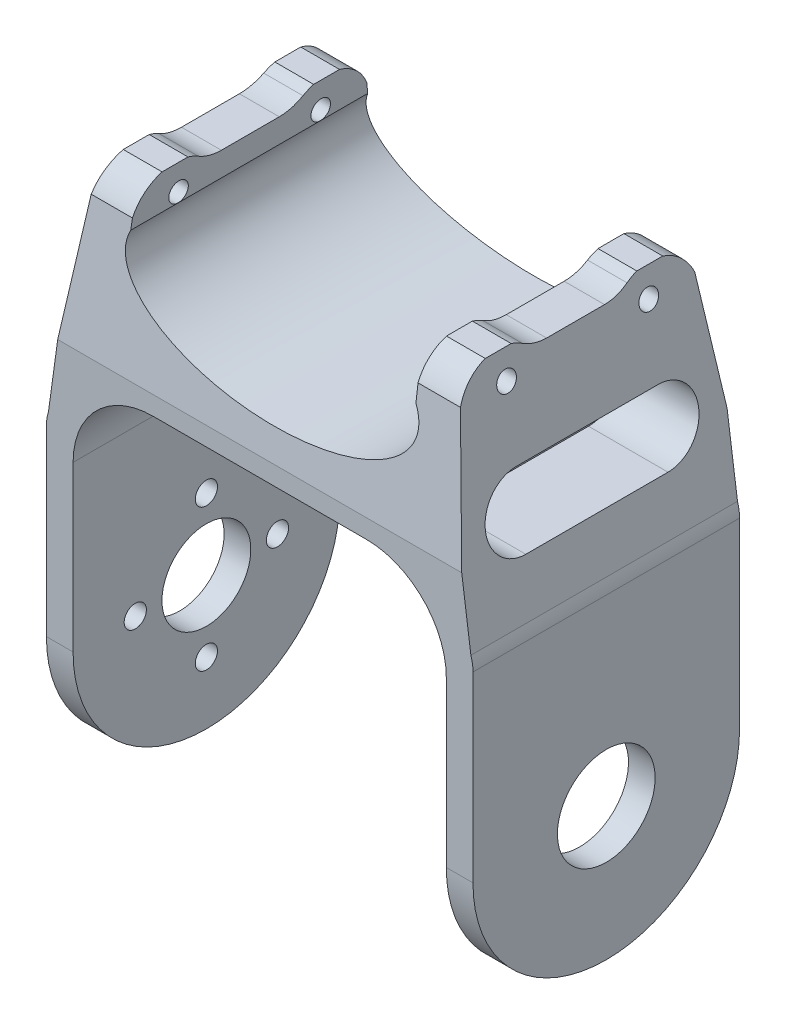
SolidWorks part; units mm, degrees
note: The reader was unsure of these and kept them because the rebuilt part matched: shared geometry of "Эскиз3<4>".
ref_plane "Спереди" through (0, 0, 0) normal (0, 0, 1) x (1, 0, 0)
ref_plane "Сверху" through (0, 0, 0) normal (0, 1, 0) x (1, 0, 0)
ref_plane "Справа" through (0, 0, 0) normal (1, 0, 0) x (0, 0, -1)
sketch "Эскиз1" plane through (0, 0, 0) normal (0, 0, 1) x (1, 0, 0)
  line L0 (-0.5529, 19.3299) -> (-0.5529, 52.5803) construction
  line L1 (-0.5529, 19.3299) -> (-0.5529, -49.2992) construction
  line L2 (23.2129, 9.6952) -> (19.8144, 34.416)
  line L3 (-21.5529, -27.3669) -> (-24.5529, -27.3669)
  line L4 (-16.7372, 30.3068) -> (-16.5529, 34.416)
  line L5 (-21.5529, -27.3669) -> (-21.5529, 5.955)
  line L6 (-24.5529, -27.3669) -> (-24.5529, 8.1828)
  line L7 (-20.9202, 34.416) -> (-16.5529, 34.416)
  line L8 (-24.3187, 9.6952) -> (-20.9202, 34.416)
  line L15 (-0.5529, 46.1948) -> (-0.6138, 46.2579)
  line L16 (-21.5529, 5.955) -> (-21.5529, 6.1114)
  line L17 (11.4471, 15.1114) -> (-12.5529, 15.1114)
  line L21 (15.4471, 29.6011) -> (15.4471, 34.416)
  line L24 (20.4471, 5.955) -> (20.4471, 6.1114)
  line L25 (-0.5529, 46.1948) -> (-0.492, 46.2579)
  line L34 (23.4471, -27.3669) -> (23.4471, 8.1828)
  line L35 (20.4471, -27.3669) -> (20.4471, 5.955)
  line L36 (19.8144, 34.416) -> (15.4471, 34.416)
  line L37 (20.4471, -27.3669) -> (23.4471, -27.3669)
  arc A0 (-12.5529, 15.1114) -> (-21.5529, 6.1114) centre (-12.5529, 6.1114) ccw
  arc A1 (11.4471, 15.1114) -> (20.4471, 6.1114) centre (11.4471, 6.1114) cw
  arc A2 (23.4471, 8.1828) -> (23.2129, 9.6952) centre (18.4471, 8.1828) ccw
  arc A19 (-24.3187, 9.6952) -> (-24.5529, 8.1828) centre (-19.5529, 8.1828) ccw
  ellipse E0 centre (-0.5529, 28.1714) end of major axis (15.9987, 27.4808) minor radius 7.6153 (-16.7372, 30.3068) -> (15.4471, 29.6011) ccw
  point P40 (-0.5529, 15.1114)
  point P54 (23.4471, 8.9571)
  point P105 (-24.5529, 8.9571)
  dimension "D2" = 9
  dimension "D3" = 5
  dimension "D5" = 21
  dimension "D10" = 61.7828
  dimension "D1" = 37.0621
  dimension "D4" = 16
  dimension "D6" = 24
  dimension "D7" = 187.828
  dimension "D8" = 9.1563
  dimension "D13" = 34.416
  dimension "D16" = 0.5529
  dimension "D17" = 27.3669
  dimension "D18" = 23.7658
  dimension "D29" = 5.4606
extrude "Бобышка-Вытянуть1" add sketch "Эскиз1" along normal blind 30
sketch "Эскиз2" plane through (23.4471, 0, 0) normal (1, 0, 0) x (0, 0, -1)
  line L0 (-15, -27.3669) -> (-15, 46.6662) construction
  line L1 (-30, -27.3669) -> (0, -27.3669) construction
  line L2 (-6.4725, 34.6331) -> (-23.5275, 34.6331)
  line L3 (-30.3535, 34.9521) -> (-23.5275, 34.6331)
  line L4 (0.5091, 34.9531) -> (-6.4725, 34.6331)
  line L5 (0.5091, 14.4531) -> (0.5091, 34.9531)
  line L6 (-1.8152, 31.4521) -> (0.5091, 14.4531)
  line L7 (-11.7404, 33.1331) -> (-18.2596, 33.1331)
  line L9 (-30.3535, 14.4521) -> (-30.3535, 34.9521)
  line L11 (-23.5275, 34.6331) -> (-15, 34.6331)
  line L14 (-30.3535, 14.4521) -> (-28.1848, 31.4521)
  arc A0 (-23.5275, 34.6331) -> (-28.1848, 31.4521) centre (-23.5275, 29.6331) ccw
  arc A1 (-20.8935, 33.8831) -> (-28.1848, 31.4521) centre (-23.5275, 29.6331) ccw
  arc A2 (-18.2596, 33.1331) -> (-20.8935, 33.8831) centre (-18.2596, 38.1331) cw
  arc A3 (-11.7404, 33.1331) -> (-9.1065, 33.8831) centre (-11.7404, 38.1331) ccw
  arc A4 (-9.1065, 33.8831) -> (-1.8152, 31.4521) centre (-6.4725, 29.6331) cw
  arc A5 (-6.4725, 34.6331) -> (-1.8152, 31.4521) centre (-6.4725, 29.6331) cw
  point P29 (-15, 33.1331)
  point P30 (-15, 34.6331)
  dimension "D3" = 20.5
  dimension "D5" = 5
  dimension "D6" = 5
  dimension "D1" = 7.27
  dimension "D2" = 62
  dimension "D4" = 20.5
  dimension "D7" = 1.5
  dimension "D8" = 6.9817
  dimension "D9" = 26.3696
  dimension "D10" = 41.819
  dimension "D11" = 41.82
  dimension "D12" = 17
sketch "Эскиз3" plane through (23.4471, 0, 0) normal (1, 0, 0) x (0, 0, -1)
  line L0 (-15, -27.3669) -> (-15, 46.9077) construction
  line L1 (-30, -27.3669) -> (0, -27.3669) construction
  line L2 (-30, -12.3669) -> (0, -12.3669) construction
  circle A0 centre (-23, 31.416) radius 1.1
  circle A1 centre (-7, 31.416) radius 1.1
  circle A2 centre (-15, -12.3669) radius 5
  arc A3 (-30, -12.3669) -> (0, -12.3669) centre (-15, -12.3669) ccw
  dimension "D1" = 8
  dimension "D2" = 2.2
  dimension "D3" = 2.2
  dimension "D5" = 30
  dimension "D4" = 31.416
extrude "Вырез-Вытянуть5" cut sketch "Эскиз3" against normal blind 56 contours A2 | A3 L2 A0 | A3 A0 L0
extrude "Вырез-Вытянуть12" cut sketch "Эскиз2" against normal blind 51 contours A0 L3 L9 L14 | L7 L0 L2 A1 A2 | L0 L7 A3 A4 L2 | L4 A4 L6 L5
extrude "Вырез-Вытянуть7" cut sketch "Эскиз3<4>" against normal blind 56 contours A0 | A1
sketch "Эскиз3<4>" plane through (23.4471, 0, 0) normal (1, 0, 0) x (0, 0, -1) same geometry as "Эскиз3"
sketch "Эскиз5" plane through (23.4471, 0, 0) normal (1, 0, 0) x (0, 0, -1)
  line L0 (-15, -37.4383) -> (-15, 43.4678) construction
  line L1 (-15, -12.3669) -> (-15, 15.6331)
  line L2 (-15, 15.6331) -> (-15, 23.6331)
  line L3 (-15, 23.6331) -> (-23, 23.6331)
  line L5 (-23, 15.6331) -> (-7, 15.6331)
  line L7 (-7, 23.6331) -> (-15, 23.6331)
  circle A1 centre (-15, -12.3669) radius 5.5
  arc A2 (-23, 15.6331) -> (-23, 23.6331) centre (-23, 19.6331) cw
  arc A3 (-7, 15.6331) -> (-7, 23.6331) centre (-7, 19.6331) ccw
  dimension "D1" = 11
  dimension "D4" = 8
  dimension "D2" = 28
  dimension "D3" = 8
sketch "Эскиз6" plane through (-24.5529, 0, 0) normal (-1, 0, 0) x (0, 0, 1)
  line L0 (15, -37.3669) -> (15, -8.1968) construction
  line L1 (0, -12.3669) -> (30, -12.3669) construction
  circle A0 centre (15, -12.3669) radius 8
  circle A2 centre (15, -4.3669) radius 1.25
  circle A3 centre (7, -12.3669) radius 1.25
  circle A4 centre (23, -12.3669) radius 1.25
  circle A5 centre (15, -20.3669) radius 1.25
  dimension "D1" = 2.5
  dimension "D2" = 16
  dimension "D3" = 2.5
  dimension "D4" = 2.5
  dimension "D5" = 2.5
extrude "Вырез-Вытянуть9" cut sketch "Эскиз6" against normal blind 22 contours A2 | A4 | A5 | A3
extrude "Вырез-Вытянуть13" cut sketch "Эскиз5" against normal blind 10 contours L3 A2 L5 A3 L7 | A1
